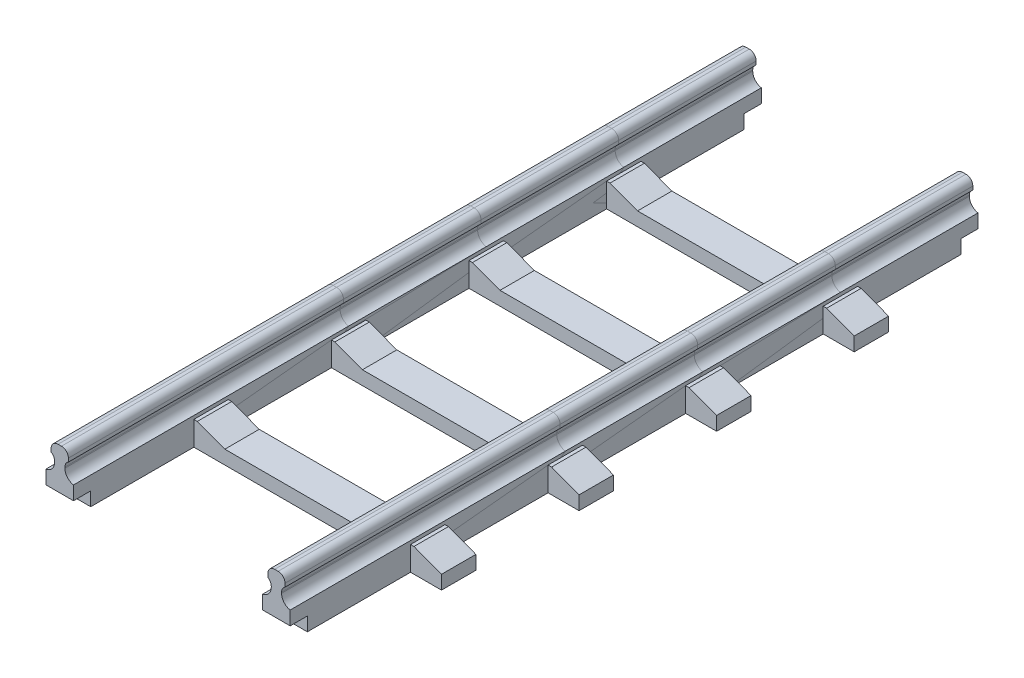
SolidWorks part; units mm, degrees
other "标注1"
sketch "草图3" plane through (-22.25, 4, -10) normal (-0.231, 0.6469, -0.7268) x (-0.9696, -0.2151, 0.1167)
other "标注2"
sketch "草图4" plane through (22.25, 8, -30) normal (0.0083, 0.0567, -0.9984) x (-0.9991, 0.0415, -0.0059)
ref_plane "前视基准面" through (0, 0, 0) normal (0, 0, 1) x (1, 0, 0)
ref_plane "上视基准面" through (0, 0, 0) normal (0, 1, 0) x (1, 0, 0)
ref_plane "右视基准面" through (0, 0, 0) normal (1, 0, 0) x (0, 0, -1)
other "Configuration Table"
sketch "草图1" plane through (0, 0, 0) normal (0, 1, 0) x (1, 0, 0)
  line L0 (-13.75, 11.25) -> (-13.75, -11.25)
  line L13 (-17.75, -11.25) -> (17.75, -11.25)
  line L21 (-17.75, -11.25) -> (-17.75, 11.25)
  line L22 (-17.75, 11.25) -> (17.75, 11.25)
  line L23 (17.75, -11.25) -> (17.75, 11.25)
  line L24 (-17.75, -11.25) -> (17.75, 11.25) construction
  line L25 (-17.75, 11.25) -> (17.75, -11.25) construction
  line L27 (13.75, 11.25) -> (13.75, -11.25)
  line L29 (-13.75, 0) -> (13.75, 0) construction
  line L32 (-22.25, 11.25) -> (22.25, 11.25)
  line L33 (-22.25, 11.25) -> (-22.25, 6.25)
  line L34 (-22.25, 6.25) -> (22.25, 6.25)
  line L35 (22.25, 11.25) -> (22.25, 6.25)
  point P0 (0, 0)
  point P15 (0, 6.25)
  dimension "D3" = 27.5
  dimension "D4" = 5
  dimension "D1" = 35.5
  dimension "D2" = 22.5
  dimension "D5" = 44.5
extrude "凸台-拉伸1" add sketch "草图1" along normal blind 4 contours L34 L21 L13 L0 | L34 L27 L13 L23 | L27 L34 L23 L22 | L21 L34 L0 L22 region at (-15.75, 0, -8.75) region at (-15.75, 0, 2.5) region at (15.75, 0, -8.75) region at (15.75, 0, 2.5)
extrude "凸台-拉伸2" add sketch "草图1<7>" along normal blind 3.5 contours L34 L35 L32 L33
sketch "草图1<7>" plane through (0, 0, 0) normal (0, 1, 0) x (1, 0, 0) same geometry as "草图1"
sketch "草图2" plane through (0, 0, -11.25) normal (0, 0, -1) x (-1, 0, 0)
  line L0 (18.25, 3.5) -> (22.25, 2)
  line L1 (22.25, 3.5) -> (18.25, 3.5)
  line L2 (22.25, 3.5) -> (22.25, 2)
  line L3 (22.25, 2) -> (18.25, 2) construction
  line L4 (18.25, 3.5) -> (18.25, 2) construction
  line L5 (-22.25, 2) -> (-18.25, 3.5)
  line L6 (-22.25, 3.5) -> (-18.25, 3.5)
  line L7 (-22.25, 3.5) -> (-22.25, 2)
  line L8 (-22.25, 2) -> (-18.25, 2) construction
  line L9 (-18.25, 3.5) -> (-18.25, 2) construction
  line L10 (13.75, 3.5) -> (-13.75, 3.5) construction
  line L11 (-13.25, 3.5) -> (-9.25, 3.5)
  line L12 (-13.25, 3.5) -> (-13.25, 2) construction
  line L13 (-13.25, 2) -> (-9.25, 2) construction
  line L14 (-9.25, 3.5) -> (-9.25, 2)
  line L15 (-13.75, 3.5) -> (-13.25, 3.5) construction
  line L16 (13.25, 3.5) -> (9.25, 3.5)
  line L17 (13.25, 3.5) -> (13.25, 2) construction
  line L18 (13.25, 2) -> (9.25, 2) construction
  line L19 (9.25, 3.5) -> (9.25, 2)
  line L20 (13.25, 3.5) -> (13.75, 3.5) construction
  line L21 (17.75, 3.5) -> (18.25, 3.5) construction
  line L22 (-13.25, 3.5) -> (-9.25, 2)
  line L23 (9.25, 2) -> (13.25, 3.5)
  line L24 (-9.25, 2) -> (9.25, 2)
  line L25 (-9.25, 3.5) -> (9.25, 3.5)
  line L26 (-15.75, 4) -> (-15.75, 6.5) construction
  line L27 (14.5, 8) -> (17, 8)
  line L28 (14.5, 8) -> (14.5, 6.5)
  line L29 (14.5, 6.5) -> (17, 6.5)
  line L30 (17, 8) -> (17, 6.5)
  line L31 (-17, 8) -> (-14.5, 8)
  line L32 (-17, 8) -> (-17, 6.5)
  line L33 (-17, 6.5) -> (-14.5, 6.5)
  line L34 (-14.5, 8) -> (-14.5, 6.5)
  line L35 (-13.75, 4) -> (-17.75, 4) construction
  line L36 (15.75, 6.5) -> (15.75, 4) construction
  line L37 (17.75, 4) -> (13.75, 4) construction
  line L38 (15, 6.5) -> (15, 4)
  line L39 (16.5, 6.5) -> (16.5, 4)
  line L40 (16.5, 4) -> (15.75, 4)
  line L41 (15.75, 4) -> (15, 4)
  line L42 (-16.5, 6.5) -> (-16.5, 4)
  line L43 (-16.5, 4) -> (-15.75, 4)
  line L44 (-15.75, 4) -> (-15, 4)
  line L45 (-15, 4) -> (-15, 6.5)
  line M9 (22.25, 3.5) -> (17.75, 3.5)
  line M11 (17.75, 4) -> (13.75, 4)
  line M13 (13.75, 3.5) -> (-13.75, 3.5)
  line M15 (-13.75, 4) -> (-17.75, 4)
  line M17 (-17.75, 3.5) -> (-22.25, 3.5)
  line M18 (-22.25, 3.5) -> (-22.25, 0)
  line M20 (22.25, 0) -> (22.25, 3.5)
  dimension "D1" = 4
  dimension "D2" = 1.5
  dimension "D3" = 2.5
  dimension "D4" = 1.5
  dimension "D5" = 2.5
  dimension "D6" = 1.5
extrude "切除-拉伸1" cut sketch "草图2" against normal through all contours L14 L24 L19 M13 | L19 L23 M13 | L22 L14 M13 | L5 M18 M17 | L0 M9 M20 region at (-20.9167, 3, -11.25) region at (20.9167, 3, -11.25) region at (10.5833, 3, -11.25) region at (0, 2.75, -11.25) region at (-10.5833, 3, -11.25)
extrude "凸台-拉伸4" add sketch "草图2<3>" against normal through all contours L34 L31 L32 L33 | L45 L33 L42 M15 | L30 L27 L28 L29 | L39 L29 L38 M11 region at (-15.75, 7.25, -11.25) region at (-15.75, 5.25, -11.25) region at (15.75, 7.25, -11.25) region at (15.75, 5.25, -11.25)
sketch "草图2<3>" plane through (0, 0, -11.25) normal (0, 0, -1) x (-1, 0, 0) same geometry as "草图2"
fillet "圆角1" radius 1 4 edges at (-16.5, 6.5, 0) (-15, 6.5, 0) (15, 6.5, 0) (16.5, 6.5, 0)
fillet "圆角2" radius 1.5 4 edges at (16.5, 4, 0) (15, 4, 0) (-15, 4, 0) (-16.5, 4, 0)
fillet "圆角3" radius 1 4 edges at (-17, 8, 0) (14.5, 8, 0) (17, 8, 0) (-14.5, 8, 0)
sketch "草图5" plane through (17.75, 0, 0) normal (1, 0, 0) x (0, 0, -1)
  line L0 (-11.25, 4) -> (-11.25, 0) construction
  line L1 (-11.25, 2) -> (-8.75, 2)
  line L2 (-11.25, 2) -> (-11.25, 0)
  line L3 (-11.25, 0) -> (-8.75, 0)
  line L4 (-8.75, 2) -> (-8.75, 0)
  line L5 (-11.25, 0) -> (6.25, 0) construction
  dimension "D1" = 2.5
  dimension "D2" = 2
extrude "切除-拉伸2" cut sketch "草图5" against normal through all
sketch "草图10" plane through (0, 2, 0) normal (0, -1, 0) x (1, 0, 0)
  line L0 (13.75, 11.25) -> (17.75, 8.75) construction
  line L1 (13.75, 11.25) -> (17.75, 11.25) construction
  line L2 (13.75, 8.75) -> (13.75, 11.25) construction
  line L3 (13.75, 8.75) -> (17.75, 8.75) construction
  line L4 (17.75, 8.75) -> (17.75, 11.25) construction
  line L5 (-17.75, 11.25) -> (-13.75, 8.75) construction
  line L6 (-17.75, 11.25) -> (-17.75, 8.75) construction
  line L7 (-17.75, 11.25) -> (-13.75, 11.25) construction
  line L8 (-13.75, -6.25) -> (-13.75, 8.75) construction
  line L9 (-17.75, 8.75) -> (-13.75, 8.75) construction
  circle A0 centre (15.75, 10) radius 0.4
  circle A1 centre (-15.75, 10) radius 0.4
  dimension "D1" = 0.8
extrude "切除-拉伸3" cut sketch "草图10" against normal blind 2
sketch "草图8" plane through (22.25, 0, 0) normal (1, 0, 0) x (0, 0, -1)
  line L0 (8.75, 0) -> (8.75, 18.5305)
  line L1 (11.25, 0) -> (6.25, 0) construction
ref_plane "基准面1" through (0, 0, -8.75) normal (0, 0, -1) x (-1, 0, 0)
mirror "镜向1" about plane through (0, 0, -8.75) normal (0, 0, -1) of bodies 202 196
pattern_linear "阵列(线性)2" count 4 spacing 20 along (0, 0, -1) of bodies 197 192
